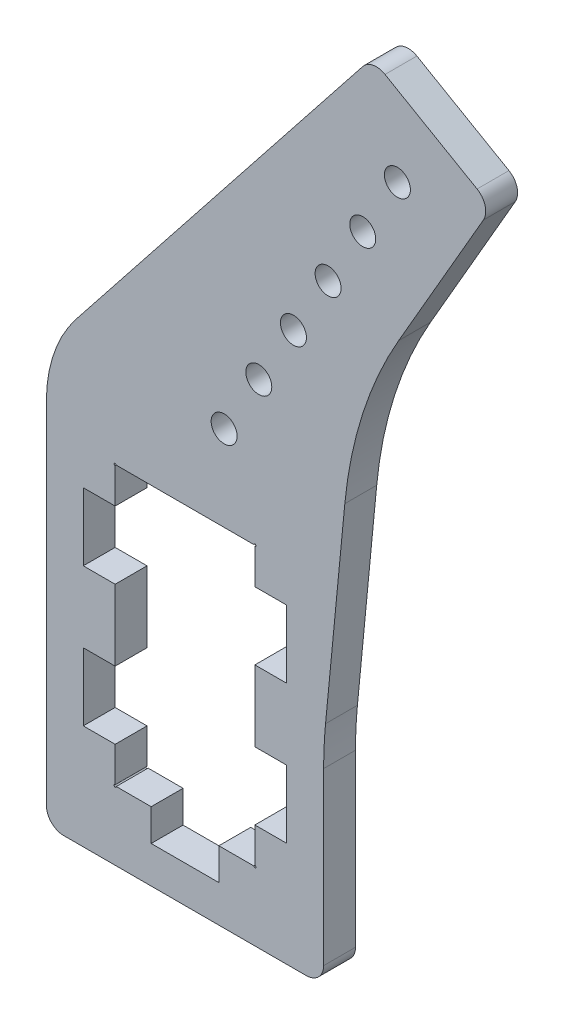
SolidWorks part; units mm, degrees
ref_plane "Front Plane" through (0, 0, 0) normal (0, 0, 1) x (1, 0, 0)
ref_plane "Top Plane" through (0, 0, 0) normal (0, 1, 0) x (1, 0, 0)
ref_plane "Right Plane" through (0, 0, 0) normal (1, 0, 0) x (0, 0, -1)
sketch "Sketch1" plane through (0, 0, 0) normal (0, 0, 1) x (1, 0, 0)
  line L0 (-5.5309, 19.15) -> (73.7115, 156.4017) construction
  line L1 (-12.8, -25.5) -> (-6.2, -25.5)
  line L2 (-12.8, -25.5) -> (-12.8, -18.9)
  line L3 (-12.8, 25.5) -> (12.8, 25.5)
  line L4 (12.8, -25.5) -> (12.8, -18.9)
  line L5 (-12.8, -25.5) -> (12.8, 25.5) construction
  line L6 (-12.8, 25.5) -> (12.8, -25.5) construction
  line L7 (25.4, -38.1) -> (-25.4, -38.1)
  line L8 (25.4, -38.1) -> (25.4, 0)
  line L9 (-12.8, 0) -> (12.8, 0) construction
  line L10 (-25.4, -38.1) -> (-25.4, 38.1)
  line L11 (25.4, -38.1) -> (-25.4, 38.1) construction
  line L12 (25.4, 38.1) -> (-25.4, -38.1) construction
  line L13 (84.71, 150.0517) -> (62.7129, 162.7517) construction
  line L14 (62.7129, 162.7517) -> (-16.5294, 25.5) construction
  line L15 (-16.5294, 25.5) -> (12.8, 25.5) construction
  line L16 (84.71, 150.0517) -> (12.8, 25.5) construction
  line L17 (-16.5294, 25.5) -> (5.4677, 12.8) construction
  line L18 (56.2677, 100.7882) -> (34.2706, 113.4882)
  line L19 (34.2706, 113.4882) -> (-25.4, 38.1)
  line L20 (56.2677, 100.7882) -> (30.8677, 56.7941)
  line L21 (30.8677, 56.7941) -> (25.4, 0)
  line L22 (0, 25.5) -> (0, -25.5) construction
  line L23 (6.2, -25.5) -> (12.8, -25.5)
  line L24 (-6.2, -31.342) -> (6.2, -31.342)
  line L25 (-6.2, -31.342) -> (-6.2, -25.5)
  line L26 (-18.642, 18.9) -> (-12.8, 18.9)
  line L27 (6.2, -31.342) -> (6.2, -25.5)
  line L28 (-6.2, -31.342) -> (6.2, -25.5) construction
  line L29 (-6.2, -25.5) -> (6.2, -31.342) construction
  line L30 (-18.642, -18.9) -> (-12.8, -18.9)
  line L31 (-18.642, -18.9) -> (-18.642, -6.5)
  line L32 (-18.642, -6.5) -> (-12.8, -6.5)
  line L34 (-18.642, -18.9) -> (-12.8, -6.5) construction
  line L35 (-18.642, -6.5) -> (-12.8, -18.9) construction
  line L36 (-18.642, 18.9) -> (-18.642, 6.5)
  line L37 (-18.642, 6.5) -> (-12.8, 6.5)
  line L38 (18.642, 18.9) -> (12.8, 18.9)
  line L39 (18.642, 6.5) -> (12.8, 6.5)
  line L40 (18.642, -6.5) -> (12.8, -6.5)
  line L41 (18.642, -18.9) -> (12.8, -18.9)
  line L42 (18.642, 18.9) -> (18.642, 6.5)
  line L43 (18.642, -18.9) -> (18.642, -6.5)
  line L44 (-12.8, 18.9) -> (-12.8, 25.5)
  line L45 (12.8, 18.9) -> (12.8, 25.5)
  line L46 (12.8, -6.5) -> (12.8, 6.5)
  line L47 (-12.8, -6.5) -> (-12.8, 6.5)
  circle A0 centre (7.1691, 41.147) radius 2.3812
  circle A1 centre (13.5191, 52.1456) radius 2.3812
  circle A2 centre (19.8691, 63.1441) radius 2.3813
  circle A3 centre (26.2191, 74.1426) radius 2.3812
  circle A4 centre (32.5691, 85.1411) radius 2.3812
  circle A8 centre (38.9191, 96.1397) radius 2.3812
  point P0 (0, 0)
  point P6 (0, 0)
  point P45 (0, -28.421)
  point P50 (-15.721, -12.7)
  dimension "D7" = 4.7625
  dimension "D1" = 25.6
  dimension "D2" = 51
  dimension "D3" = 50.8
  dimension "D4" = 76.2
  dimension "D5" = 25.4
  dimension "D6" = 60
  dimension "D8" = 25.4
  dimension "D9" = 25.4
  dimension "D10" = 12.7
  dimension "D11" = 50.8
  dimension "D12" = 12.4
  dimension "D13" = 5.842
  dimension "D14" = 5.842
  dimension "D15" = 12.4
  dimension "D16" = 12.7
extrude "Boss-Extrude1" add sketch "Sketch1" along normal blind 5.842
fillet "Fillet1" radius 3.175 4 edges at (-25.4, -38.1, 2.921) (25.4, -38.1, 2.921) (34.2706, 113.4882, 2.921) (56.2677, 100.7882, 2.921)
fillet "Fillet3" radius 76.2 2 edges at (25.4, 0, 2.921) (30.8677, 56.7941, 2.921)
fillet "Fillet4" radius 25.4 1 edges at (-25.4, 38.1, 2.921)
sketch "Sketch2" plane through (0, 0, 5.842) normal (0, 0, 1) x (1, 0, 0)
  circle A0 centre (-12.8, 25.5) radius 0.1984
  circle A1 centre (12.8, 25.5) radius 0.1984
  circle A2 centre (12.8, -25.5) radius 0.1984
  circle A3 centre (-12.8, -25.5) radius 0.1984
  dimension "D1" = 0.3969
  dimension "D2" = 0.3969
  dimension "D3" = 0.3969
  dimension "D4" = 0.3969
extrude "Cut-Extrude1" cut sketch "Sketch2" against normal through all
sketch "Sketch3" plane through (0, 0, 5.842) normal (0, 0, 1) x (1, 0, 0)
  line L0 (18.642, 12.7) -> (-28.575, 12.7) construction
  line L1 (18.642, 6.5) -> (18.642, 18.9) construction
  line L2 (18.642, -12.7) -> (-28.575, -12.7) construction
  line L3 (18.642, -18.9) -> (18.642, -6.5) construction
  line L4 (-25.4, 29.2642) -> (-25.4, -34.925) construction
  line L5 (-31.75, -18.9) -> (-25.4, -22.075)
  line L6 (-12.8, 0) -> (12.8, 0) construction
  line L7 (-12.8, 6.5) -> (-12.8, -6.5) construction
  line L8 (12.8, -6.5) -> (12.8, 6.5) construction
  line L9 (-31.75, 6.5) -> (-25.4, 18.9) construction
  line L10 (-31.75, 18.9) -> (-25.4, 6.5) construction
  line L11 (-25.4, 3.325) -> (-25.4, 6.5)
  line L12 (-31.75, 6.5) -> (-25.4, 3.325)
  line L13 (-31.75, -18.9) -> (-31.75, -6.5)
  line L14 (-25.4, 22.075) -> (-25.4, 18.9)
  line L15 (-25.4, -18.9) -> (-25.4, -6.5)
  line L16 (-31.75, -18.9) -> (-25.4, -6.5) construction
  line L17 (-31.75, -6.5) -> (-25.4, -18.9) construction
  line L18 (-25.4, -22.075) -> (-25.4, -18.9)
  line L19 (-31.75, -6.5) -> (-25.4, -3.325)
  line L20 (-25.4, -3.325) -> (-25.4, -6.5)
  line L21 (-25.4, 18.9) -> (-25.4, 6.5)
  line L22 (-31.75, 18.9) -> (-31.75, 6.5)
  line L23 (-31.75, 18.9) -> (-25.4, 22.075)
  dimension "D2" = 3.175
  dimension "D3" = 3.175
  dimension "D4" = 3.175
extrude "Boss-Extrude2" [suppressed] add sketch "Sketch3" against normal up to surface (5.842 mm away)
fillet "Fillet5" [suppressed] radius 3.175
